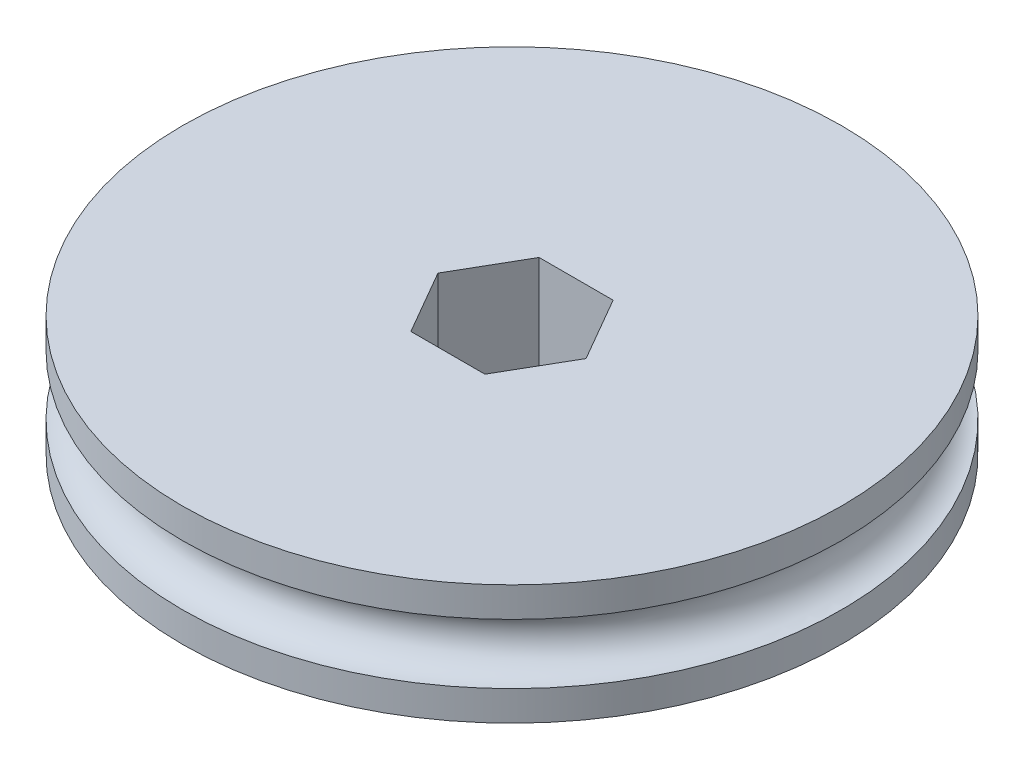
SolidWorks part; units mm, degrees
ref_plane "Front" through (0, 0, 0) normal (0, 0, 1) x (1, 0, 0)
ref_plane "Top" through (0, 0, 0) normal (0, 1, 0) x (1, 0, 0)
ref_plane "Right" through (0, 0, 0) normal (1, 0, 0) x (0, 0, -1)
sketch "Sketch1" plane through (0, 0, 0) normal (0, 1, 0) x (1, 0, 0)
  line L1 (7.8456, 0) -> (3.9228, 6.7945)
  line L2 (3.9228, 6.7945) -> (-3.9228, 6.7945)
  line L3 (-3.9228, 6.7945) -> (-7.8456, 0)
  line L4 (-7.8456, 0) -> (-3.9228, -6.7945)
  line L5 (-3.9228, -6.7945) -> (3.9228, -6.7945)
  line L6 (3.9228, -6.7945) -> (7.8456, 0)
  circle A0 centre (0, 0) radius 6.7945 construction
  circle A1 centre (0, 0) radius 34.925
  dimension "D1" = 69.85
extrude "Boss-Extrude1" add sketch "Sketch1" along normal blind 12.7
ref_plane "Mid_Plane" through (0, 6.35, 0) normal (0, -1, 0) x (-1, 0, 0)
sketch "Sketch4" plane through (-6.35, 6.35, 0) normal (0, 0, -1) x (0, 1, 0)
  line L0 (-6.35, 6.35) -> (-6.35, 41.275) construction
  line L1 (-6.35, 41.275) -> (0, 41.275) construction
  line L3 (6.35, 41.275) -> (-6.35, 41.275) construction
  line L4 (0, 41.275) -> (6.35, 41.275) construction
  line L5 (-6.35, 41.275) -> (-6.35, -28.575) construction
  circle A1 centre (0, 41.275) radius 3.175
  point P7 (0, 0)
  point P12 (0, 0)
  dimension "D3" = 6.35
ref_axis "Axis1" through (0, 12.7, 0) along (0, -1, 0)
revolve "Cut-Revolve1" cut sketch "Sketch4" angle 360 about axis through (0, 12.7, 0) along (0, -1, 0)
